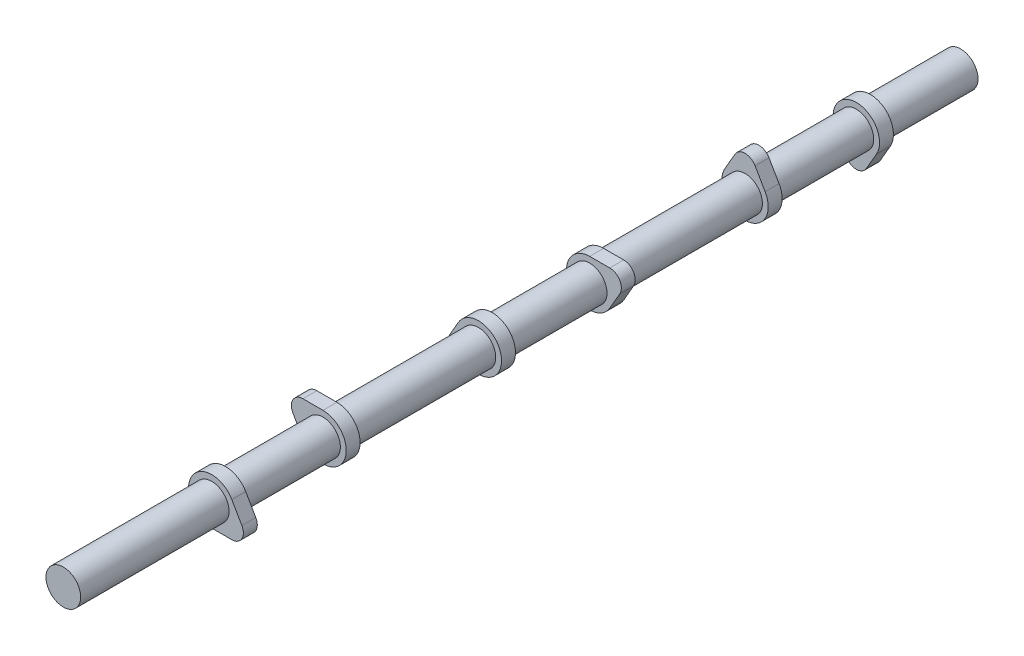
SolidWorks part; units mm, degrees
ref_plane "Front Plane" through (0, 0, 0) normal (0, 0, 1) x (1, 0, 0)
ref_plane "Top Plane" through (0, 0, 0) normal (0, 1, 0) x (1, 0, 0)
ref_plane "Right Plane" through (0, 0, 0) normal (1, 0, 0) x (0, 0, -1)
sketch "Sketch1" plane through (0, 0, 0) normal (0, 0, 1) x (1, 0, 0)
  line L0 (-5.4993, 15.875) -> (-10.9985, 6.35)
  line L1 (5.4993, 15.875) -> (10.9985, 6.35)
  arc A0 (-10.9985, 6.35) -> (10.9985, 6.35) centre (0, 0) ccw
  arc A1 (5.4993, 15.875) -> (-5.4993, 15.875) centre (0, 12.7) ccw
  dimension "D1" = 25.4
  dimension "D2" = 12.7
  dimension "D3" = 12.7
extrude "Boss-Extrude1" add sketch "Sketch1" along normal mid plane 7.62
ref_axis "Axis1" through (0, 0, 55.5936) along (0, 0, -1)
move or copy body "Body-Move/Copy1" bodies to move or copy 101 copy yes number of copies 1 translate (0, 0, 60.96)
move or copy body "Body-Move/Copy2" bodies to move or copy 101 copy no rotation origin (0, 0, 0) rotation axis (0, 0, 1) rotation angle 180
sketch "Sketch2" plane through (0, 0, 0) normal (0, 0, 1) x (1, 0, 0)
  circle A0 centre (0, 0) radius 9.5
  dimension "D1" = 19
extrude "Boss-Extrude2" add sketch "Sketch2" along normal blind 146.05 from offset 25.4 offset against normal yes
pattern_linear "LPattern1" count 3 spacing 146.05 along (0, 0, 1) of bodies 104
move or copy body "Body-Move/Copy3" bodies to move or copy 105 copy no rotation origin (0, 0, 0) rotation axis (0, 0, 1) rotation angle 120
move or copy body "Body-Move/Copy4" bodies to move or copy 106 copy no rotation origin (0, 0, 0) rotation axis (0, 0, -1) rotation angle 120
sketch "Sketch3" plane through (0, 0, -25.4) normal (0, 0, -1) x (-1, 0, 0)
  circle A1 centre (0, 0) radius 9.5
  circle A2 centre (0, 0) radius 9.5
  dimension "D1" = 0
extrude "Boss-Extrude3" add sketch "Sketch3" along normal blind 27.94
combine bodies "Combine1" operation type add bodies to combine 109 107 108
sketch "Sketch5" plane through (0, 0, 412.75) normal (0, 0, 1) x (1, 0, 0)
  circle A1 centre (0, 0) radius 9.5
  circle A2 centre (0, 0) radius 9.5
  dimension "D1" = 0
extrude "Boss-Extrude4" add sketch "Sketch5" along normal blind 25.4
